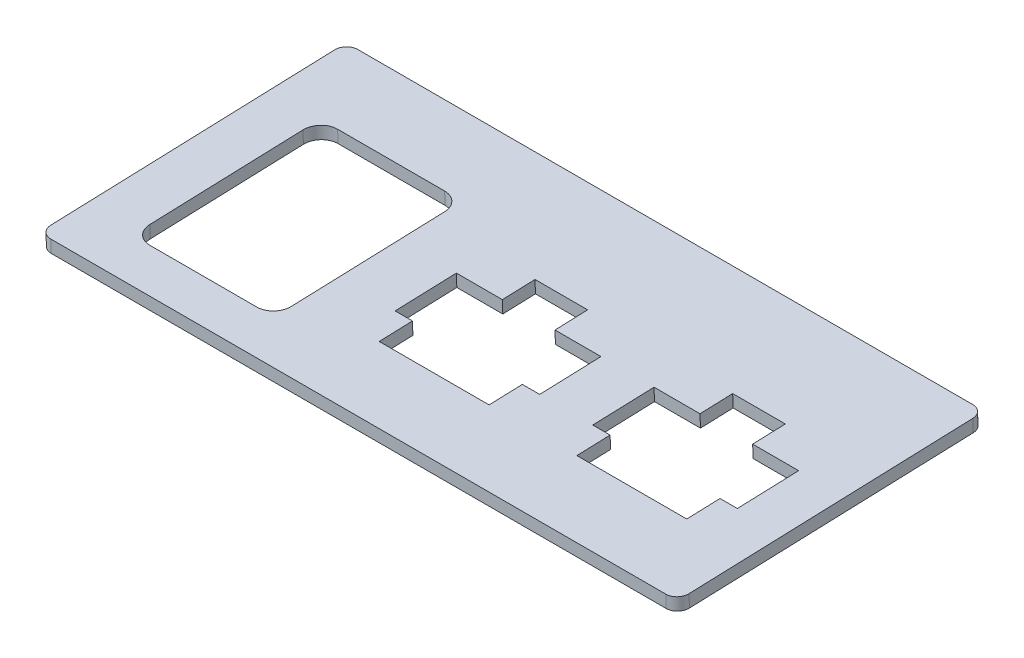
SolidWorks part; units mm, degrees
ref_plane "Front Plane" through (0, 0, 0) normal (0, 0, 1) x (1, 0, 0)
ref_plane "Top Plane" through (0, 0, 0) normal (0, 1, 0) x (1, 0, 0)
ref_plane "Right Plane" through (0, 0, 0) normal (1, 0, 0) x (0, 0, -1)
sketch "Sketch1" plane through (0, -71.9872, -2.5138) normal (0, 0.9994, 0.0349) x (1, 0, 0)
  line L0 (-56.175, 49.6404) -> (56.175, 49.6404) construction
  line L1 (-52.175, -2.9116) -> (-56.175, -2.9116) construction
  line L8 (-55.175, -4.2116) -> (55.175, -4.2116)
  line L9 (55.175, -4.2116) -> (55.175, 48.8904)
  line L10 (55.175, 48.8904) -> (-55.175, 48.8904)
  line L11 (-55.175, 48.8904) -> (-55.175, -4.2116)
  dimension "D4" = 0.75
  dimension "D1" = 1.3
  dimension "D2" = 3.0034
  dimension "D3" = 3.0034
extrude "Boss-Extrude1" add sketch "Sketch1" along normal blind 2.2
sketch "Sketch2" plane through (0, -71.9872, -2.5138) normal (0, -0.9994, -0.0349) x (1, 0, 0)
  line L0 (-4.05, -24.7624) -> (-4.05, -30.4124)
  line L1 (-43.425, -3.1624) -> (-24.925, -3.1624)
  line L2 (-46.425, -6.1624) -> (-46.425, -32.6624)
  line L3 (-43.425, -35.6624) -> (-24.925, -35.6624)
  line L4 (-21.925, -6.1624) -> (-21.925, -32.6624)
  line L5 (-12, -14.1624) -> (-9, -14.1624)
  line L6 (-12, -14.1624) -> (-12, -24.7624)
  line L7 (-12, -24.7624) -> (-4.05, -24.7624)
  line L8 (13, -14.1624) -> (13, -24.7624)
  line L9 (-9, -8.4124) -> (10, -8.4124)
  line L10 (-9, -8.4124) -> (-9, -14.1624)
  line L11 (-4.05, -30.4124) -> (5.05, -30.4124)
  line L12 (10, -8.4124) -> (10, -14.1624)
  line L13 (10, -14.1624) -> (13, -14.1624)
  line L14 (5.05, -24.7624) -> (5.05, -30.4124)
  line L15 (5.05, -24.7624) -> (13, -24.7624)
  line L16 (-13, -5.9124) -> (14, -32.9124) construction
  line L17 (-13, -5.9124) -> (14, -5.9124) construction
  line L18 (-13, -5.9124) -> (-13, -32.9124) construction
  line L19 (-13, -32.9124) -> (14, -32.9124) construction
  line L20 (14, -5.9124) -> (14, -32.9124) construction
  line L21 (17.5875, 3.7502) -> (17.5875, -36.664) construction
  line L22 (47.175, -19.4624) -> (22.175, -19.4624) construction
  line L23 (34.675, -8.4124) -> (34.675, -30.4124) construction
  line L24 (21.175, -5.9124) -> (21.175, -32.9124) construction
  line L25 (48.175, -32.9124) -> (21.175, -32.9124) construction
  line L26 (48.175, -5.9124) -> (48.175, -32.9124) construction
  line L27 (48.175, -5.9124) -> (21.175, -5.9124) construction
  line L28 (-48.175, -19.4124) -> (-46.425, -19.4124) construction
  line L29 (-48.175, -1.4124) -> (-20.175, -1.4124) construction
  line L30 (-48.175, -1.4124) -> (-48.175, -37.4124) construction
  line L31 (-48.175, -37.4124) -> (-20.175, -37.4124) construction
  line L32 (-20.175, -1.4124) -> (-20.175, -37.4124) construction
  line L33 (-34.175, -3.1624) -> (-34.175, -1.4124) construction
  line L34 (0.5, -8.4124) -> (0.5, -30.4124) construction
  line L35 (-12, -19.4624) -> (13, -19.4624) construction
  line L36 (48.175, -5.9124) -> (21.175, -32.9124) construction
  line L37 (30.125, -24.7624) -> (22.175, -24.7624)
  line L38 (30.125, -24.7624) -> (30.125, -30.4124)
  line L39 (25.175, -14.1624) -> (22.175, -14.1624)
  line L40 (25.175, -8.4124) -> (25.175, -14.1624)
  line L41 (39.225, -30.4124) -> (30.125, -30.4124)
  line L42 (44.175, -8.4124) -> (44.175, -14.1624)
  line L43 (44.175, -8.4124) -> (25.175, -8.4124)
  line L44 (22.175, -14.1624) -> (22.175, -24.7624)
  line L45 (47.175, -24.7624) -> (39.225, -24.7624)
  line L46 (47.175, -14.1624) -> (47.175, -24.7624)
  line L47 (47.175, -14.1624) -> (44.175, -14.1624)
  line L48 (39.225, -24.7624) -> (39.225, -30.4124)
  line L49 (21.175, -19.4124) -> (14, -19.4124) construction
  line L51 (48.175, -19.4124) -> (52.175, -19.4124) construction
  line L52 (55.175, 4.2116) -> (55.175, -48.8904) construction
  line L53 (-46.7565, -41.6404) -> (46.7565, -41.6404) construction
  line L54 (-13, -19.4124) -> (-20.175, -19.4124) construction
  line L55 (-34.175, -1.4124) -> (-34.175, 2.8156) construction
  line L56 (-34.175, -37.4124) -> (-34.175, -41.6404) construction
  line L57 (-55.175, -48.8904) -> (-55.175, 4.2116) construction
  line L58 (-48.175, -19.4124) -> (-52.175, -19.4124) construction
  line L59 (-53.075, 2.8156) -> (53.075, 2.8156) construction
  arc A0 (-46.425, -32.6624) -> (-43.425, -35.6624) centre (-43.425, -32.6624) ccw
  arc A1 (-24.925, -35.6624) -> (-21.925, -32.6624) centre (-24.925, -32.6624) ccw
  arc A2 (-24.925, -3.1624) -> (-21.925, -6.1624) centre (-24.925, -6.1624) cw
  arc A3 (-43.425, -3.1624) -> (-46.425, -6.1624) centre (-43.425, -6.1624) ccw
  point P28 (0.5, -19.4124)
  point P63 (34.675, -19.4124)
  dimension "D1" = 3
  dimension "D2" = 32.5
  dimension "D3" = 24.5
  dimension "D4" = 28
  dimension "D5" = 36
  dimension "D6" = 25
  dimension "D7" = 22
  dimension "D8" = 10.6
  dimension "D9" = 19
  dimension "D10" = 9.1
  dimension "D11" = 5.75
  dimension "D12" = 27
  dimension "D13" = 27
  dimension "D14" = 4
  dimension "D15" = 3
  dimension "D16" = 3
extrude "Cut-Extrude1" cut sketch "Sketch2" against normal up to next
fillet "Fillet1" radius 2 4 edges at (-55.175, -71.0348, 1.7336) (55.175, -71.0348, 1.7336) (55.175, -69.1816, -51.336) (-55.175, -69.1816, -51.336)
